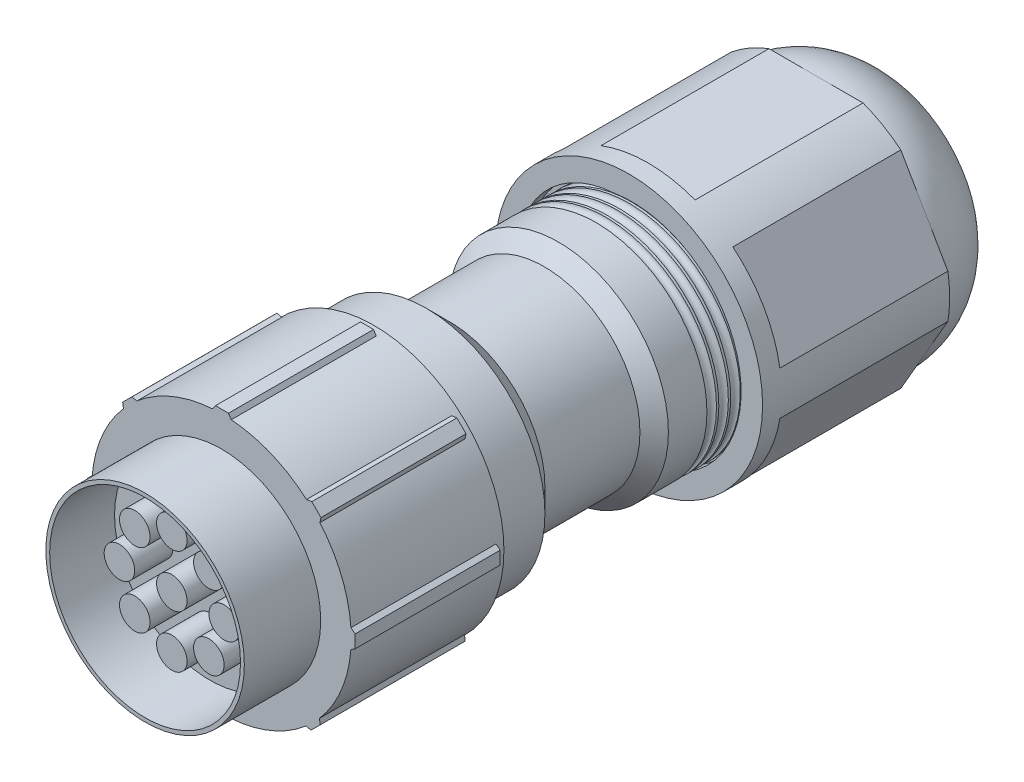
SolidWorks part; units mm, degrees
ref_plane "Front Plane" through (0, 0, 0) normal (0, 0, 1) x (1, 0, 0)
ref_plane "Top Plane" through (0, 0, 0) normal (0, 1, 0) x (1, 0, 0)
ref_plane "Right Plane" through (0, 0, 0) normal (1, 0, 0) x (0, 0, -1)
sketch "Sketch1" plane through (0, 0, 0) normal (0, 0, 1) x (1, 0, 0)
  circle A0 centre (0, 0) radius 8.5
  dimension "D1" = 17
extrude "Boss-Extrude1" add sketch "Sketch1" against normal blind 10
sketch "Sketch2" plane through (0, 0, 0) normal (0, 0, 1) x (1, 0, 0)
  circle A0 centre (0, 0) radius 6.5
  dimension "D1" = 13
extrude "Boss-Extrude2" add sketch "Sketch2" along normal blind 5
sketch "Sketch3" plane through (0, 0, 0) normal (1, 0, 0) x (0, 0, -1)
  line L0 (10, 7.7662) -> (13.4193, 7.7662)
  line L2 (10, -8.5) -> (10, 8.5) construction
  line L3 (13.4193, 7.7662) -> (14.9223, 6.2632)
  line L4 (14.9223, 6.2632) -> (21.1445, 6.2632)
  line L5 (21.1445, 6.2632) -> (22.0763, 7.195)
  line L6 (22.0763, 7.195) -> (23.94, 7.195)
  line L7 (23.94, 7.195) -> (23.94, 0)
  line L8 (23.94, 0) -> (10, 0)
  line L9 (10, 0) -> (10, 7.7662)
revolve "Revolve1" add sketch "Sketch3" angle 360 about L8
sketch "Sketch4" plane through (0, 0, -23.94) normal (0, 0, -1) x (-1, 0, 0)
  circle A0 centre (0, 0) radius 7.195
extrude "Boss-Extrude3" add sketch "Sketch4" along normal blind 3.5
sketch "Sketch5" plane through (0, 0, -27.44) normal (0, 0, -1) x (-1, 0, 0)
  circle A0 centre (0, 0) radius 7.195 construction
  circle A1 centre (0, 0) radius 7.195
curve "Helix/Spiral1" pitch 0.7778 height 3.5 turns 4.5
sketch "Sketch6" plane through (0, 0, 0) normal (1, 0, 0) x (0, 0, -1)
  circle A1 centre (27.44, -7.195) radius 0.3122
sweep "Cut-Sweep2" cut profiles "Sketch6" path "Helix/Spiral1"
sketch "Sketch7" plane through (0, 0, -27.44) normal (0, 0, -1) x (-1, 0, 0)
  circle A0 centre (0, 0) radius 8.75
  dimension "D1" = 17.5
extrude "Boss-Extrude5" add sketch "Sketch7" along normal blind 11.5
sketch "Sketch8" plane through (0, 0, 0) normal (1, 0, 0) x (0, 0, -1)
  line L0 (38.94, -8.75) -> (38.94, 8.75) construction
  line L2 (38.94, 0) -> (38.94, 8.1909)
  line L4 (41.9978, 0) -> (38.94, 0)
  line L5 (43.1551, 6.3625) -> (43.1551, 0)
  line L6 (43.1551, 0) -> (41.9978, 0)
  arc A0 (38.94, 8.1909) -> (43.1551, 6.3625) centre (39.249, 3.1304) cw
revolve "Revolve3" add sketch "Sketch8" angle 360 about L4
sketch "Sketch10" plane through (0, 0, -43.1551) normal (0, 0, -1) x (-1, 0, 0)
  circle A0 centre (0, 0) radius 3
  dimension "D1" = 6
extrude "Cut-Extrude1" cut sketch "Sketch10" against normal blind 3
sketch "Sketch11" plane through (0, 0, 5) normal (0, 0, 1) x (1, 0, 0)
  circle A0 centre (0, 0) radius 6.25
  dimension "D1" = 12.5
extrude "Cut-Extrude2" cut sketch "Sketch11" against normal blind 4.25
sketch "Sketch12" plane through (0, 0, 0.75) normal (0, 0, 1) x (1, 0, 0)
  circle A0 centre (0, 0) radius 1
  circle A1 centre (0, 3.43) radius 1
  dimension "D1" = 2
  dimension "D2" = 2
  dimension "D3" = 3.43
extrude "Boss-Extrude6" add sketch "Sketch12" along normal blind 2.5
pattern_circular "CirPattern1" count 8 over 360 about axis through (0, 0, 0) along (0, 0, 1) of "Boss-Extrude6"
sketch "Sketch14" plane through (0, 0, 0) normal (0, 0, 1) x (1, 0, 0)
  line L10 (0.0229, 8.5) -> (0.0229, 8.4712)
  line L11 (0.0229, 8.4712) -> (0.6429, 8.4757)
  line L12 (0.0229, 8.4712) -> (-0.5971, 8.479)
  line L13 (-0.5971, 8.479) -> (-0.3883, 8.759)
  line L14 (0.6429, 8.4757) -> (0.4618, 8.7557)
  line L15 (-0.3883, 8.759) -> (0.4618, 8.7557)
  circle A3 centre (0, 0) radius 8.5 construction
  dimension "D1" = 0.62
  dimension "D2" = 0.62
  dimension "D3" = 0.28
  dimension "D4" = 0.28
extrude "Boss-Extrude7" add sketch "Sketch14" against normal blind 9.5
pattern_circular "CirPattern2" count 8 over 360 about axis through (0, 0, 0) along (0, 0, 1) of "Boss-Extrude7"
sketch "Sketch15" plane through (0, 0, -27.44) normal (0, 0, 1) x (1, 0, 0)
  arc A0 (-0.9885, 8.694) -> (-8.75, 0) centre (0, 0) ccw
  circle A1 centre (0, 0) radius 8.75 construction
  arc A2 (-8.75, 0) -> (-0.3082, -8.7446) centre (0, 0) ccw
  arc A3 (8.75, 0) -> (-0.3082, -8.7446) centre (0, 0) cw
  arc A4 (8.75, 0) -> (-0.9885, 8.694) centre (0, 0) ccw
  arc A5 (-0.9885, 7.1742) -> (-7.2763, 0) centre (-0.5453, 0.4432) ccw
  arc A6 (-7.2763, 0) -> (-2.2166, -7.0118) centre (-0.132, -0.1761) ccw
  arc A7 (-2.2166, -7.0118) -> (7.0803, 2.028) centre (-0.0575, 0.0683) ccw
  arc A8 (7.0803, 2.028) -> (-0.9885, 7.1742) centre (0.2001, 0.139) ccw
extrude "Boss-Extrude8" add sketch "Sketch15" along normal blind 0.75
sketch "Sketch16" plane through (0, 0, -38.94) normal (0, 0, -1) x (-1, 0, 0)
  line L0 (-0.0296, 8.8518) -> (-3.5296, 8.8518)
  line L1 (-3.5296, 8.8518) -> (-3.5296, 8.1896)
  line L2 (-0.0296, 8.8518) -> (3.4704, 8.8518)
  line L3 (-3.5296, 8.1896) -> (3.4704, 8.1896)
  line L4 (3.4704, 8.1896) -> (3.4704, 8.8518)
  dimension "D1" = 3.5
  dimension "D2" = 3.5
  dimension "D3" = 7
extrude "Cut-Extrude3" cut sketch "Sketch16" against normal blind 11
pattern_circular "CirPattern3" count 6 over 360 about axis through (0, 0, 0) along (0, 0, 1) of "Cut-Extrude3"
